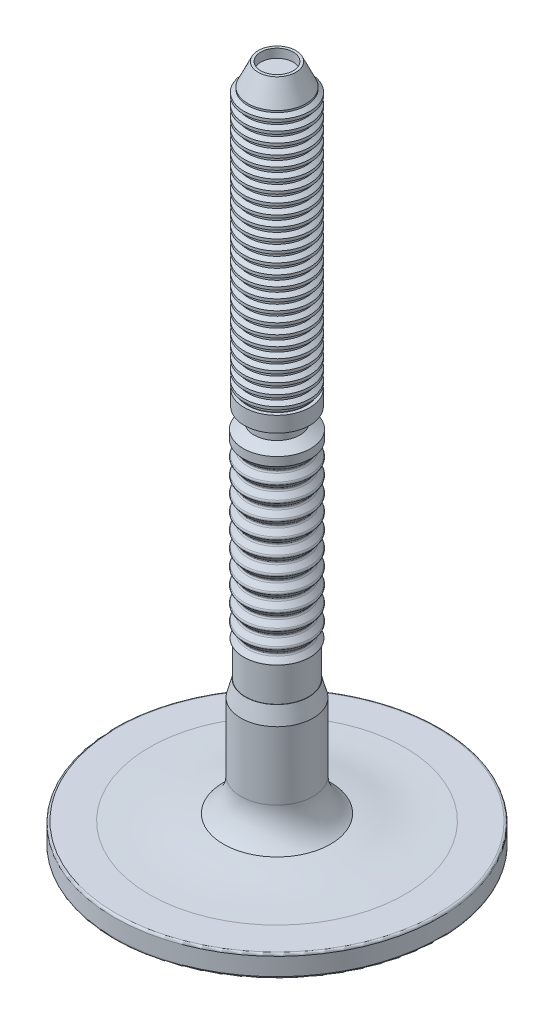
SolidWorks part; units mm, degrees
material "1023 Carbon Steel Sheet (SS)"
ref_plane "Front Plane" through (0, 0, 0) normal (0, 0, 1) x (1, 0, 0)
ref_plane "Top Plane" through (0, 0, 0) normal (0, 1, 0) x (1, 0, 0)
ref_plane "Right Plane" through (0, 0, 0) normal (1, 0, 0) x (0, 0, -1)
sketch "Sketch1" plane through (0, 0, 0) normal (0, 1, 0) x (1, 0, 0)
  circle A0 centre (0, 0) radius 18.5
  dimension "D1" = 37
extrude "Boss-Extrude1" add sketch "Sketch1" along normal blind 2.5
sketch "Sketch2" plane through (0, 2.5, 0) normal (0, 1, 0) x (1, 0, 0)
  circle A0 centre (0, 0) radius 4.1
  dimension "D1" = 8.2
extrude "Boss-Extrude2" add sketch "Sketch2" along normal blind 14
sketch "Sketch3" plane through (0, 16.5, 0) normal (0, 1, 0) x (1, 0, 0)
  circle A0 centre (0, 0) radius 3.575
  dimension "D1" = 7.15
extrude "Boss-Extrude3" add sketch "Sketch3" along normal blind 4
sketch "Sketch4" plane through (0, 20.5, 0) normal (0, 1, 0) x (1, 0, 0)
  circle A0 centre (0, 0) radius 3.825
  dimension "D1" = 7.65
extrude "Boss-Extrude4" add sketch "Sketch4" along normal blind 21.3
sketch "Sketch5" plane through (0, 41.8, 0) normal (0, 1, 0) x (1, 0, 0)
  circle A0 centre (0, 0) radius 2.6
  dimension "D1" = 5.2
extrude "Boss-Extrude5" add sketch "Sketch5" along normal blind 0.75
sketch "Sketch6" plane through (0, 42.55, 0) normal (0, 1, 0) x (1, 0, 0)
  circle A0 centre (0, 0) radius 3.725
  dimension "D1" = 7.45
extrude "Boss-Extrude6" add sketch "Sketch6" along normal blind 2.5
sketch "Sketch7" plane through (0, 45.05, 0) normal (0, 1, 0) x (1, 0, 0)
  circle A0 centre (0, 0) radius 3.75
  dimension "D1" = 7.5
extrude "Boss-Extrude7" add sketch "Sketch7" along normal blind 32.2
chamfer "Chamfer2" distance 0.739 angle 60 1 edges at (0, 41.8, 3.825) first distance on face at (0, 41.8, 3.825)
chamfer "Chamfer3" distance 0.739 angle 60 1 edges at (0, 42.55, 3.725) first distance on face at (0, 45.05, 3.725)
chamfer "Chamfer4" distance 1.835 angle 15 1 edges at (0, 16.5, 4.1) first distance on face at (0, 16.5, 4.1)
sketch "Sketch12" plane through (0, 0, 0) normal (0, 0, 1) x (1, 0, 0)
  line L0 (3.244, 25.0466) -> (-3.244, 25.0466) construction
  line L1 (0, 0) -> (0, 79.9408) construction
  line L2 (-3.825, 41.061) -> (-3.825, 40.061)
  line L3 (-3.825, 20.5) -> (3.825, 20.5) construction
  line L4 (-3.244, 20.5) -> (-3.244, 41.061) construction
  line L5 (-3.825, 41.061) -> (3.825, 41.061) construction
  line L6 (-3.825, 40.061) -> (-3.3171, 39.4557)
  line L7 (-3.575, 20.5) -> (3.575, 20.5) construction
  line L8 (3.244, 20.5) -> (3.244, 41.061) construction
  line L9 (-3.244, 39.2549) -> (-3.244, 39.2518)
  line L10 (-3.3171, 39.051) -> (-3.7656, 38.5164)
  line L11 (-3.3171, 37.251) -> (-3.7656, 36.7164)
  line L12 (-3.7656, 36.3903) -> (-3.3171, 35.8557)
  line L13 (-3.7656, 38.1903) -> (-3.3171, 37.6557)
  line L14 (-3.3171, 35.451) -> (-3.7656, 34.9164)
  line L15 (-3.7656, 34.5903) -> (-3.3171, 34.0557)
  line L16 (-3.3171, 33.651) -> (-3.7656, 33.1164)
  line L17 (-3.7656, 32.7903) -> (-3.3171, 32.2557)
  line L18 (-3.3171, 31.851) -> (-3.7656, 31.3164)
  line L19 (-3.7656, 30.9903) -> (-3.3171, 30.4557)
  line L20 (-3.3171, 30.051) -> (-3.7656, 29.5164)
  line L21 (-3.7656, 29.1903) -> (-3.3171, 28.6557)
  line L22 (-3.3171, 28.251) -> (-3.7656, 27.7164)
  line L23 (-3.7656, 27.3903) -> (-3.3171, 26.8557)
  line L24 (-3.3171, 26.451) -> (-3.7656, 25.9164)
  line L25 (-3.7656, 25.5903) -> (-3.3171, 25.0557)
  line L26 (-3.3171, 24.651) -> (-3.7656, 24.1164)
  line L27 (-3.7656, 23.7903) -> (-3.3171, 23.2557)
  line L28 (-3.3171, 22.851) -> (-3.7656, 22.3164)
  line L29 (-3.7656, 21.9903) -> (-3.3171, 21.4557)
  line L30 (-3.3171, 21.051) -> (-3.7656, 20.5164)
  line L31 (-3.244, 21.2518) -> (-3.244, 21.2549)
  line L32 (-3.7656, 20.1903) -> (-3.244, 19.5686) [skipped]
  line L33 (-3.7783, 20.5) -> (-4.0498, 20.5)
  line L34 (-4.0498, 20.5) -> (-4.0498, 41.061)
  line L35 (-4.0498, 41.061) -> (-3.825, 41.061)
  line L36 (-3.244, 23.0518) -> (-3.244, 23.0549)
  line L37 (-3.244, 24.8518) -> (-3.244, 24.8549)
  line L38 (-3.244, 26.6518) -> (-3.244, 26.6549)
  line L39 (-3.244, 28.4518) -> (-3.244, 28.4549)
  line L40 (-3.244, 30.2518) -> (-3.244, 30.2549)
  line L41 (-3.244, 32.0518) -> (-3.244, 32.0549)
  line L42 (-3.244, 33.8518) -> (-3.244, 33.8549)
  line L43 (-3.244, 35.6518) -> (-3.244, 35.6549)
  line L44 (-3.244, 37.4518) -> (-3.244, 37.4549)
  arc A0 (-3.7656, 38.5164) -> (-3.7656, 38.1903) centre (-3.5713, 38.3533) ccw
  arc A1 (-3.244, 39.2518) -> (-3.3171, 39.051) centre (-3.5565, 39.2518) cw
  arc A2 (-3.3171, 39.4557) -> (-3.244, 39.2549) centre (-3.5565, 39.2549) cw
  arc A3 (-3.3171, 37.6557) -> (-3.244, 37.4549) centre (-3.5565, 37.4549) cw
  arc A4 (-3.244, 37.4518) -> (-3.3171, 37.251) centre (-3.5565, 37.4518) cw
  arc A5 (-3.7656, 36.7164) -> (-3.7656, 36.3903) centre (-3.5713, 36.5533) ccw
  arc A6 (-3.3171, 35.8557) -> (-3.244, 35.6549) centre (-3.5565, 35.6549) cw
  arc A7 (-3.244, 35.6518) -> (-3.3171, 35.451) centre (-3.5565, 35.6518) cw
  arc A8 (-3.7656, 34.9164) -> (-3.7656, 34.5903) centre (-3.5713, 34.7533) ccw
  arc A9 (-3.3171, 34.0557) -> (-3.244, 33.8549) centre (-3.5565, 33.8549) cw
  arc A10 (-3.244, 33.8518) -> (-3.3171, 33.651) centre (-3.5565, 33.8518) cw
  arc A11 (-3.7656, 33.1164) -> (-3.7656, 32.7903) centre (-3.5713, 32.9533) ccw
  arc A12 (-3.3171, 32.2557) -> (-3.244, 32.0549) centre (-3.5565, 32.0549) cw
  arc A13 (-3.244, 32.0518) -> (-3.3171, 31.851) centre (-3.5565, 32.0518) cw
  arc A14 (-3.7656, 31.3164) -> (-3.7656, 30.9903) centre (-3.5713, 31.1533) ccw
  arc A15 (-3.3171, 30.4557) -> (-3.244, 30.2549) centre (-3.5565, 30.2549) cw
  arc A16 (-3.244, 30.2518) -> (-3.3171, 30.051) centre (-3.5565, 30.2518) cw
  arc A17 (-3.7656, 29.5164) -> (-3.7656, 29.1903) centre (-3.5713, 29.3533) ccw
  arc A18 (-3.3171, 28.6557) -> (-3.244, 28.4549) centre (-3.5565, 28.4549) cw
  arc A19 (-3.244, 28.4518) -> (-3.3171, 28.251) centre (-3.5565, 28.4518) cw
  arc A20 (-3.7656, 27.7164) -> (-3.7656, 27.3903) centre (-3.5713, 27.5533) ccw
  arc A21 (-3.3171, 26.8557) -> (-3.244, 26.6549) centre (-3.5565, 26.6549) cw
  arc A22 (-3.244, 26.6518) -> (-3.3171, 26.451) centre (-3.5565, 26.6518) cw
  arc A23 (-3.7656, 25.9164) -> (-3.7656, 25.5903) centre (-3.5713, 25.7533) ccw
  arc A24 (-3.3171, 25.0557) -> (-3.244, 24.8549) centre (-3.5565, 24.8549) cw
  arc A25 (-3.244, 24.8518) -> (-3.3171, 24.651) centre (-3.5565, 24.8518) cw
  arc A26 (-3.7656, 24.1164) -> (-3.7656, 23.7903) centre (-3.5713, 23.9533) ccw
  arc A27 (-3.3171, 23.2557) -> (-3.244, 23.0549) centre (-3.5565, 23.0549) cw
  arc A28 (-3.244, 23.0518) -> (-3.3171, 22.851) centre (-3.5565, 23.0518) cw
  arc A29 (-3.7656, 22.3164) -> (-3.7656, 21.9903) centre (-3.5713, 22.1533) ccw
  arc A30 (-3.3171, 21.4557) -> (-3.244, 21.2549) centre (-3.5565, 21.2549) cw
  arc A31 (-3.244, 21.2518) -> (-3.3171, 21.051) centre (-3.5565, 21.2518) cw
  arc A32 (-3.7656, 20.5164) -> (-3.7783, 20.5) centre (-3.5713, 20.3533) ccw
  point P3 (0, 25.0466)
  point P24 (-3.244, 39.1381)
  point P30 (-3.244, 39.3686)
  dimension "D9" = 0.2537
  dimension "D10" = 0.3125
  dimension "D1" = 6.488
  dimension "D2" = 0
  dimension "D3" = 1
  dimension "D5" = 140
  dimension "D6" = 140
  dimension "D7" = 0.2305
  dimension "D8" = 140
  dimension "D11" = 11
revolve "Cut-Revolve1" cut sketch "Sketch12" angle 360 about L1
sketch "Sketch13" plane through (0, 0, 0) normal (0, 0, 1) x (1, 0, 0)
  line L0 (0, 0) -> (0, 79.8538) construction
  line L1 (-3.3095, 50.5688) -> (3.3095, 50.5688) construction
  line L2 (3.3095, 50.5688) -> (3.3095, 81.5967) construction
  line L3 (3.3095, 74.55) -> (3.75, 74.216)
  line L4 (3.75, 45.05) -> (3.75, 77.25) construction
  line L6 (3.3095, 75.05) -> (3.3095, 74.55)
  line L7 (3.75, 74.216) -> (3.75, 73.897)
  line L8 (3.75, 73.897) -> (3.3095, 73.72)
  line L9 (3.3095, 73.72) -> (3.3095, 73.371)
  line L10 (3.3095, 72.541) -> (3.3095, 72.192)
  line L11 (3.75, 72.718) -> (3.3095, 72.541)
  line L12 (3.75, 73.037) -> (3.75, 72.718)
  line L13 (3.3095, 73.371) -> (3.75, 73.037)
  line L14 (3.3095, 71.362) -> (3.3095, 71.013)
  line L15 (3.75, 71.539) -> (3.3095, 71.362)
  line L16 (3.75, 71.858) -> (3.75, 71.539)
  line L17 (3.3095, 72.192) -> (3.75, 71.858)
  line L18 (3.3095, 70.183) -> (3.3095, 69.834)
  line L19 (3.75, 70.36) -> (3.3095, 70.183)
  line L20 (3.75, 70.679) -> (3.75, 70.36)
  line L21 (3.3095, 71.013) -> (3.75, 70.679)
  line L22 (3.3095, 69.004) -> (3.3095, 68.655)
  line L23 (3.75, 69.181) -> (3.3095, 69.004)
  line L24 (3.75, 69.5) -> (3.75, 69.181)
  line L25 (3.3095, 69.834) -> (3.75, 69.5)
  line L26 (3.3095, 67.825) -> (3.3095, 67.476)
  line L27 (3.75, 68.002) -> (3.3095, 67.825)
  line L28 (3.75, 68.321) -> (3.75, 68.002)
  line L29 (3.3095, 68.655) -> (3.75, 68.321)
  line L30 (3.3095, 66.646) -> (3.3095, 66.297)
  line L31 (3.75, 66.823) -> (3.3095, 66.646)
  line L32 (3.75, 67.142) -> (3.75, 66.823)
  line L33 (3.3095, 67.476) -> (3.75, 67.142)
  line L34 (3.3095, 65.467) -> (3.3095, 65.118)
  line L35 (3.75, 65.644) -> (3.3095, 65.467)
  line L36 (3.75, 65.963) -> (3.75, 65.644)
  line L37 (3.3095, 66.297) -> (3.75, 65.963)
  line L38 (3.3095, 64.288) -> (3.3095, 63.939)
  line L39 (3.75, 64.465) -> (3.3095, 64.288)
  line L40 (3.75, 64.784) -> (3.75, 64.465)
  line L41 (3.3095, 65.118) -> (3.75, 64.784)
  line L42 (3.3095, 63.109) -> (3.3095, 62.76)
  line L43 (3.75, 63.286) -> (3.3095, 63.109)
  line L44 (3.75, 63.605) -> (3.75, 63.286)
  line L45 (3.3095, 63.939) -> (3.75, 63.605)
  line L46 (3.3095, 61.93) -> (3.3095, 61.581)
  line L47 (3.75, 62.107) -> (3.3095, 61.93)
  line L48 (3.75, 62.426) -> (3.75, 62.107)
  line L49 (3.3095, 62.76) -> (3.75, 62.426)
  line L50 (3.3095, 60.751) -> (3.3095, 60.402)
  line L51 (3.75, 60.928) -> (3.3095, 60.751)
  line L52 (3.75, 61.247) -> (3.75, 60.928)
  line L53 (3.3095, 61.581) -> (3.75, 61.247)
  line L54 (3.3095, 59.572) -> (3.3095, 59.223)
  line L55 (3.75, 59.749) -> (3.3095, 59.572)
  line L56 (3.75, 60.068) -> (3.75, 59.749)
  line L57 (3.3095, 60.402) -> (3.75, 60.068)
  line L58 (3.3095, 58.393) -> (3.3095, 58.044)
  line L59 (3.75, 58.57) -> (3.3095, 58.393)
  line L60 (3.75, 58.889) -> (3.75, 58.57)
  line L61 (3.3095, 59.223) -> (3.75, 58.889)
  line L62 (3.3095, 57.214) -> (3.3095, 56.865)
  line L63 (3.75, 57.391) -> (3.3095, 57.214)
  line L64 (3.75, 57.71) -> (3.75, 57.391)
  line L65 (3.3095, 58.044) -> (3.75, 57.71)
  line L66 (3.3095, 56.035) -> (3.3095, 55.686)
  line L67 (3.75, 56.212) -> (3.3095, 56.035)
  line L68 (3.75, 56.531) -> (3.75, 56.212)
  line L69 (3.3095, 56.865) -> (3.75, 56.531)
  line L70 (3.3095, 54.856) -> (3.3095, 54.507)
  line L71 (3.75, 55.033) -> (3.3095, 54.856)
  line L72 (3.75, 55.352) -> (3.75, 55.033)
  line L73 (3.3095, 55.686) -> (3.75, 55.352)
  line L74 (3.3095, 53.677) -> (3.3095, 53.328)
  line L75 (3.75, 53.854) -> (3.3095, 53.677)
  line L76 (3.75, 54.173) -> (3.75, 53.854)
  line L77 (3.3095, 54.507) -> (3.75, 54.173)
  line L78 (3.3095, 52.498) -> (3.3095, 52.149)
  line L79 (3.75, 52.675) -> (3.3095, 52.498)
  line L80 (3.75, 52.994) -> (3.75, 52.675)
  line L81 (3.3095, 53.328) -> (3.75, 52.994)
  line L82 (3.3095, 51.319) -> (3.3095, 50.97)
  line L83 (3.75, 51.496) -> (3.3095, 51.319)
  line L84 (3.75, 51.815) -> (3.75, 51.496)
  line L85 (3.3095, 52.149) -> (3.75, 51.815)
  line L86 (3.3095, 50.14) -> (3.3095, 49.791)
  line L87 (3.75, 50.317) -> (3.3095, 50.14)
  line L88 (3.75, 50.636) -> (3.75, 50.317)
  line L89 (3.3095, 50.97) -> (3.75, 50.636)
  line L90 (3.3095, 48.961) -> (3.3095, 48.612)
  line L91 (3.75, 49.138) -> (3.3095, 48.961)
  line L92 (3.75, 49.457) -> (3.75, 49.138)
  line L93 (3.3095, 49.791) -> (3.75, 49.457)
  line L94 (3.3095, 47.782) -> (3.3095, 47.433)
  line L95 (3.75, 47.959) -> (3.3095, 47.782)
  line L96 (3.75, 48.278) -> (3.75, 47.959)
  line L97 (3.3095, 48.612) -> (3.75, 48.278)
  line L98 (3.3095, 46.603) -> (3.3095, 46.254)
  line L99 (3.75, 46.78) -> (3.3095, 46.603)
  line L100 (3.75, 47.099) -> (3.75, 46.78)
  line L101 (3.3095, 47.433) -> (3.75, 47.099)
  line L102 (3.3095, 45.424) -> (3.3095, 45.075)
  line L103 (3.75, 45.601) -> (3.3095, 45.424)
  line L104 (3.75, 45.92) -> (3.75, 45.601)
  line L105 (3.3095, 46.254) -> (3.75, 45.92)
  line L106 (3.75, 45.05) -> (5.1368, 45.05)
  line L107 (5.1368, 45.05) -> (5.1368, 75.05)
  line L109 (3.3095, 45.075) -> (3.3425, 45.05)
  line L110 (3.75, 45.05) -> (3.3425, 45.05)
  line L112 (3.3095, 75.05) -> (3.3095, 77.6165)
  line L113 (3.75, 44.741) -> (3.75, 44.422) [skipped]
  line L114 (3.75, 44.422) -> (3.3095, 44.245) [skipped]
  line L115 (3.3095, 44.245) -> (3.3095, 43.896) [skipped]
  line L116 (3.3095, 77.6165) -> (5.1368, 77.6165)
  line L117 (5.1368, 77.6165) -> (5.1368, 75.05)
  point P6 (0, 50.5688)
  dimension "D1" = 6.619
  dimension "D2" = 0.5
  dimension "D3" = 0.334
  dimension "D4" = 0.319
  dimension "D5" = 0.177
  dimension "D6" = 0.349
  dimension "D7" = 26
revolve "Cut-Revolve2" cut sketch "Sketch13" angle 360 about L0
chamfer "Chamfer5" distance 2.5 angle 25 1 edges at (0, 77.25, 3.3095) first distance on face at (0, 77.25, 3.3095)
sketch "Sketch14" plane through (0, 77.25, 0) normal (0, 1, 0) x (1, 0, 0)
  circle A2 centre (0, 0) radius 1.8437
  circle A3 centre (0, 0) radius 1.8437
  dimension "D1" = 0.3
extrude "Cut-Extrude2" cut sketch "Sketch14" against normal blind 1
fillet "Fillet1" radius 4.453 1 edges at (0, 2.5, 4.1)
sketch "Sketch16" plane through (0, 0, 0) normal (1, 0, 0) x (0, 0, -1)
  line L0 (0, 2.5) -> (-14.5, 2.5) construction
  line L1 (18.5, 2.5) -> (-18.5, 2.5) construction
  line L2 (0, 2.5) -> (0, 3.25) construction
  line L3 (0, 3.25) -> (-14.5, 3.25) construction
  line L4 (-14.5, 3.25) -> (-14.5, 2.5) construction
  line L5 (-6.0775, 3.25) -> (-6.0775, 2.5)
  line L6 (-6.0775, 2.5) -> (-14.5, 2.5)
  spline S0 degree 3 poles (-14.5, 2.5) (-9.1911, 2.5603) (-10.0963, 2.8002) (-6.0775, 3.25) knots 0 0 0 0 1 1 1 1
  dimension "D3" = 8.4674
  dimension "D1" = 14.5
  dimension "D2" = 8.4225
  dimension "0.75" = 0.75
revolve "Revolve1" add sketch "Sketch16" angle 360 about L2
sketch "Sketch18" plane through (0, 0, 0) normal (0, 0, 1) x (1, 0, 0)
  line L0 (0, 0) -> (-6, 0)
  line L1 (-18.5, 0) -> (18.5, 0) construction
  line L2 (-6, 0) -> (-6, 0.5) construction
  line L3 (-6, 0.5) -> (-7.1, 0.5) construction
  line L4 (-7.1, 0.5) -> (-7.1, 0) construction
  line L5 (-7.1, 0) -> (-8.5, 0)
  line L6 (-8.5, 0) -> (-8.5, 0.5) construction
  line L7 (-8.5, 0.5) -> (-9.9, 0.5) construction
  line L8 (-9.9, 0.5) -> (-9.9, 0) construction
  line L9 (-9.9, 0) -> (-11.25, 0)
  line L10 (-11.25, 0) -> (-11.25, 0.5) construction
  line L11 (-11.25, 0.5) -> (-12.8, 0.5) construction
  line L12 (-12.8, 0.5) -> (-12.8, 0) construction
  line L13 (-12.8, 0) -> (-13.7, 0)
  line L14 (-13.7, 0) -> (-13.7, 0.5) construction
  line L15 (-13.7, 0.5) -> (-15.1, 0.5) construction
  line L16 (-15.1, 0.5) -> (-15.1, 0) construction
  line L17 (-15.1, 0) -> (-16.4, 0)
  line L18 (-16.4, 0) -> (-16.4, 0.5) construction
  line L19 (-16.4, 0.5) -> (-18, 0.5) construction
  line L20 (-18, 0.5) -> (-18, 0) construction
  line L21 (-18, 0) -> (-18.5, 0)
  line L22 (-18.5, 0) -> (-20.2476, 0)
  line L23 (-20.2476, 0) -> (-20.2476, -1.8403)
  line L24 (-6, 0.5) -> (-6.35, 0.5) construction
  line L25 (-8.5, 0.5) -> (-8.85, 0.5) construction
  line L26 (-11.25, 0.5) -> (-11.6, 0.5) construction
  line L27 (-13.7, 0.5) -> (-14.05, 0.5) construction
  line L28 (-16.4, 0.5) -> (-16.75, 0.5) construction
  line L29 (-6.35, 0.5) -> (-6.55, 0.5) construction
  line L30 (-8.85, 0.5) -> (-9.05, 0.5) construction
  line L31 (-11.6, 0.5) -> (-11.8, 0.5) construction
  line L32 (-14.05, 0.5) -> (-14.25, 0.5) construction
  line L33 (-16.75, 0.5) -> (-16.95, 0.5) construction
  line L34 (-6, 0.35) -> (-23.9788, 0.35) construction
  line L35 (-6.35, 0.5) -> (-6.35, 0.35) construction
  line L36 (-8.85, 0.5) -> (-8.85, 0.35) construction
  line L37 (-11.6, 0.5) -> (-11.6, 0.35) construction
  line L38 (-14.05, 0.5) -> (-14.05, 0.35) construction
  line L39 (-16.75, 0.5) -> (-16.75, 0.35) construction
  line L40 (-20.2476, -1.8403) -> (0, -1.8403)
  line L41 (0, -1.8403) -> (0, 0)
  spline S0 degree 3 poles (-16.4, 0) (-16.5585, 0.0075) (-16.6772, 0.2848) (-16.8907, 0.5184) (-17.3897, 0.443) (-17.9869, 0.0247) (-18, 0) knots 0 0 0 0 0.259428 0.377356 0.451413 1 1 1 1
  spline S1 degree 3 poles (-13.7, 0) (-13.8638, 0.0018) (-13.9749, 0.2777) (-14.188, 0.5237) (-14.6089, 0.4169) (-15.0884, 0.0258) (-15.1, 0) knots 0 0 0 0 0.285926 0.415899 0.487306 1 1 1 1
  spline S2 degree 3 poles (-11.25, 0) (-11.4133, -0.0091) (-11.5262, 0.2835) (-11.7398, 0.5229) (-12.2205, 0.4157) (-12.7874, 0.0246) (-12.8, 0) knots 0 0 0 0 0.265686 0.386458 0.459889 1 1 1 1
  spline S3 degree 3 poles (-8.5, 0) (-8.6564, 0.0057) (-8.7764, 0.282) (-8.9879, 0.5175) (-9.4088, 0.4475) (-9.8883, 0.0262) (-9.9, 0) knots 0 0 0 0 0.285926 0.415899 0.487306 1 1 1 1
  spline S4 degree 3 poles (-6, 0) (-6.1305, -0.0059) (-6.2769, 0.2919) (-6.6593, 0.6731) (-7.0719, 0.171) (-7.1, 0) knots 0 0 0 0 0.332582 0.483764 1 1 1 1
  dimension "D22" = 1.7741
  dimension "D23" = 1.5573
  dimension "D1" = 6
  dimension "0.258" = 0.5
  dimension "D2" = 7.1
  dimension "D3" = 8.5
  dimension "D4" = 9.9
  dimension "D5" = 11.25
  dimension "D6" = 12.8
  dimension "D7" = 13.7
  dimension "D8" = 15.1
  dimension "D9" = 16.4
  dimension "D10" = 18
  dimension "D11" = 0.35
  dimension "D12" = 0.35
  dimension "D13" = 0.35
  dimension "D14" = 0.35
  dimension "D15" = 0.2
  dimension "D16" = 0.2
  dimension "D17" = 0.35
  dimension "D18" = 0.2
  dimension "D19" = 0.2
  dimension "D20" = 0.2
  dimension "D21" = 0.15
revolve "Cut-Revolve3" cut sketch "Sketch18" angle 360 about L41
fillet "Fillet2" radius 0.25 2 edges at (0, 0, 18.5) (0, 2.5, 18.5)
